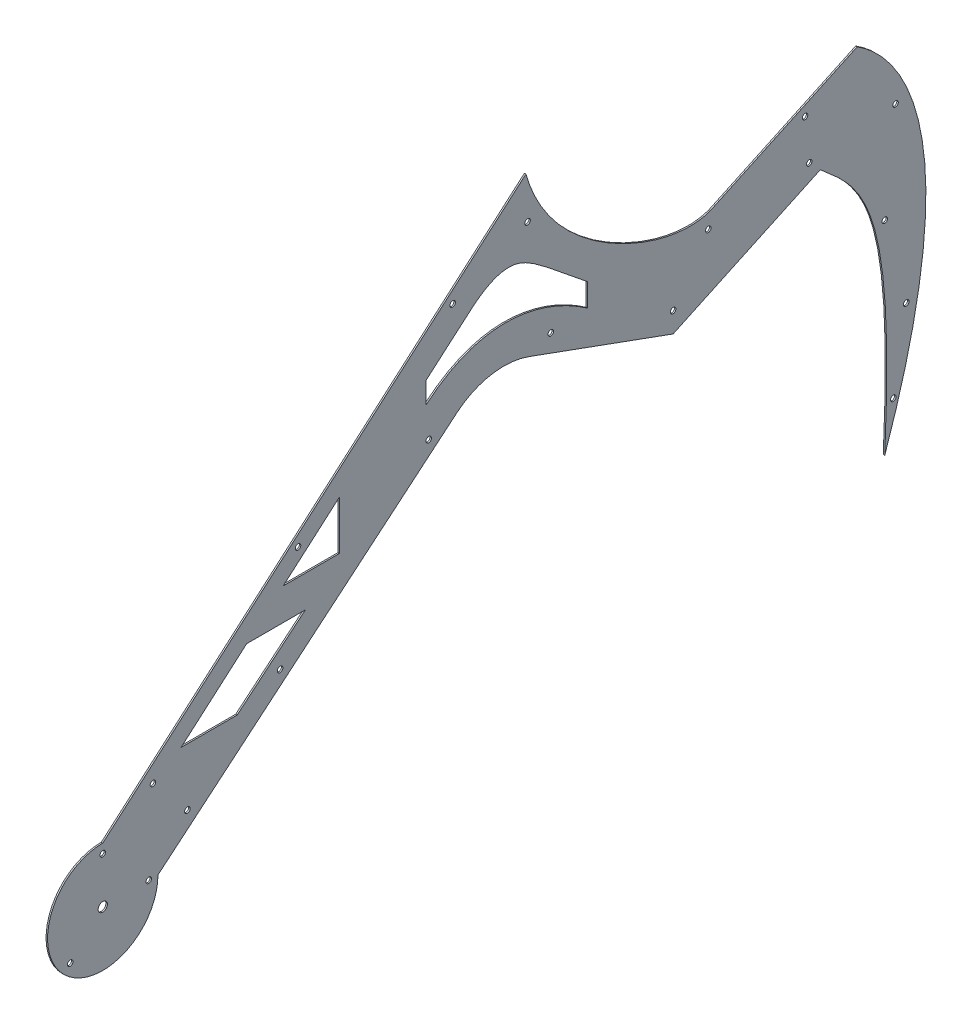
SolidWorks part; units mm, degrees
other "Markup1"
sketch "Sketch3" plane through (0, -30, -453.7149) normal (1, 0, 0) x (0, 0, -1)
ref_plane "Front Plane" through (0, 0, 0) normal (0, 0, 1) x (1, 0, 0)
ref_plane "Top Plane" through (0, 0, 0) normal (0, 1, 0) x (1, 0, 0)
ref_plane "Right Plane" through (0, 0, 0) normal (1, 0, 0) x (0, 0, -1)
sketch "Sketch2" plane through (0, 0, 0) normal (1, 0, 0) x (0, 0, -1)
  line L4 (-746.1189, 0) -> (2001.1162, 0) construction
  line L5 (0, 883.5315) -> (0, -632.2635) construction
  line L6 (0, 30) -> (230, 229.9359)
  line L7 (30, 0) -> (192.309, 136.1934)
  line L9 (231.7013, 143.1393) -> (310, 114.6409)
  line L10 (310, 114.6409) -> (390, 151.9455)
  line L11 (330, 162.4851) -> (410, 199.7897)
  line L12 (410, 199.7897) -> (437.0314, 182.9088) construction
  line L13 (437.0314, 182.9088) -> (470.3985, 130.1127) construction
  line L14 (390, 151.9455) -> (412.7624, 132.5357) construction
  line L15 (412.7624, 132.5357) -> (430.8798, 119.3594) construction
  line L16 (430.8798, 119.3594) -> (425.0344, 0) construction
  line L17 (470.3985, 130.1127) -> (425.0344, 0) construction
  line L18 (230, 229.9359) -> (239.3138, 197.0283) construction
  line L19 (239.3138, 197.0283) -> (264.964, 173.3238) construction
  line L20 (264.964, 173.3238) -> (307.757, 154.3394) construction
  line L21 (307.757, 154.3394) -> (330, 162.4851) construction
  line L22 (42.5631, 53.7494) -> (73.0482, 53.7494)
  line L24 (78.201, 84.729) -> (42.5631, 53.7494)
  line L25 (73.0482, 53.7494) -> (110.1371, 84.729)
  line L26 (110.1371, 84.729) -> (78.201, 84.729)
  line L27 (98.0934, 102.0212) -> (128.5785, 128.5214)
  line L28 (128.5785, 128.5214) -> (128.5785, 102.0212)
  line L29 (128.5785, 102.0212) -> (98.0934, 102.0212)
  line L30 (175.7455, 159.9984) -> (198.0041, 179.2063)
  line L31 (241.6174, 180.2232) -> (263.537, 162.4851)
  line L32 (198.0041, 179.2063) -> (218.9673, 198.4306) construction
  line L33 (218.9673, 198.4306) -> (227.9539, 188.9081) construction
  line L34 (227.9539, 188.9081) -> (231.4161, 188.3022) construction
  line L35 (231.4161, 188.3022) -> (241.6174, 180.2232) construction
  line L36 (175.7455, 148.428) -> (196.999, 166.4038) construction
  line L37 (196.999, 166.4038) -> (219.1847, 171.1458) construction
  line L38 (219.1847, 171.1458) -> (243.505, 164.1915) construction
  line L39 (243.505, 164.1915) -> (263.537, 150.0193) construction
  line L40 (175.7455, 159.9984) -> (175.7455, 148.428)
  line L41 (263.537, 162.4851) -> (263.537, 150.0193)
  line L42 (0, 25) -> (25, 0) construction
  line L43 (12.5, 12.5) -> (-27.6808, -27.6808) construction
  arc A0 (0, 30) -> (30, 0) centre (0, 0) ccw
  circle A1 centre (0, 0) radius 2.5
  arc A2 (192.309, 136.1934) -> (231.7013, 143.1393) centre (218.0205, 105.5516) cw
  circle A3 centre (96.409, 63.5562) radius 1.5
  circle A4 centre (25, 0) radius 1.5
  circle A5 centre (-17.6777, -17.6777) radius 1.5
  circle A6 centre (0, 25) radius 1.5
  circle A7 centre (27.2862, 44.4444) radius 1.5
  circle A8 centre (106.1435, 116.3066) radius 1.5
  circle A9 centre (177.163, 131.3169) radius 1.5
  circle A10 centre (190.1621, 188.6803) radius 1.5
  circle A11 centre (230.8867, 206.9706) radius 1.5
  circle A12 centre (243.505, 148.428) radius 1.5
  circle A13 centre (310, 125.634) radius 1.5
  circle A14 centre (329.1217, 154.3394) radius 1.5
  circle A15 centre (381.7045, 181.0784) radius 1.5
  circle A16 centre (383.9639, 158.1949) radius 1.5
  circle A17 centre (430.8798, 162.4851) radius 1.5
  circle A18 centre (425.0344, 110.6788) radius 1.5
  circle A19 centre (436.7166, 65.8476) radius 1.5
  circle A20 centre (429.6663, 24.5411) radius 1.5
  circle A21 centre (46, 22.5634) radius 1.5
  spline S0 degree 3 poles (410, 199.7897) (437.0314, 182.9088) (470.3985, 130.1127) (425.0344, 0) knots 0 0 0 0 1 1 1 1
  spline S1 degree 3 poles (390, 151.9455) (412.7624, 132.5357) (430.8798, 119.3594) (425.0344, 0) knots 0 0 0 0 1 1 1 1
  spline S2 degree 4 poles (230, 229.9359) (239.3138, 197.0283) (264.964, 173.3238) (307.757, 154.3394) (330, 162.4851) knots 0 0 0 0 0 1 1 1 1 1
  spline S3 degree 4 poles (198.0041, 179.2063) (218.9673, 198.4306) (227.9539, 188.9081) (231.4161, 188.3022) (241.6174, 180.2232) knots 0 0 0 0 0 1 1 1 1 1
  spline S4 degree 4 poles (175.7455, 148.428) (196.999, 166.4038) (219.1847, 171.1458) (243.505, 164.1915) (263.537, 150.0193) knots 0 0 0 0 0 1 1 1 1 1
  point P22 (210, 151.0379)
  dimension "D1" = 60
  dimension "D13" = 5
  dimension "D14" = 40
  dimension "D18" = 3
  dimension "D20" = 3
  dimension "D23" = 3
  dimension "D26" = 3
  dimension "D27" = 3
  dimension "D30" = 3
  dimension "D32" = 3
  dimension "D34" = 3
  dimension "D36" = 3
  dimension "D37" = 3
  dimension "D38" = 3
  dimension "D39" = 3
  dimension "D40" = 3
  dimension "D42" = 3
  dimension "D43" = 3
  dimension "D44" = 3
  dimension "D45" = 3
  dimension "D46" = 3
  dimension "D47" = 3
  dimension "D2" = 210
  dimension "D3" = 40
  dimension "D4" = 41
  dimension "D5" = 230
  dimension "D6" = 120
  dimension "D7" = 10
  dimension "D8" = 310
  dimension "D9" = 330
  dimension "D10" = 135
  dimension "D11" = 390
  dimension "D12" = 410
  dimension "D15" = 20
  dimension "D16" = 20
  dimension "D17" = 25
  dimension "D19" = 25
  dimension "D21" = 90
  dimension "D22" = 25
  dimension "D24" = 7
  dimension "D25" = 7
  dimension "D28" = 46
  dimension "D29" = 6
  dimension "D31" = 4.5
  dimension "D33" = 6
  dimension "D35" = 5
  dimension "D41" = 5
base flange "Base-Flange1" sketch "Sketch2" thickness 0.8 reverse thickness direction no parameters "D1"=0.7366
sketch "Bend-Lines1" plane through (0, 0, 0) normal (0, 1, 0) x (1, 0, 0)
sketch "Bounding-Box1" plane through (0, 0, 0) normal (0, 1, 0) x (1, 0, 0)
sheet metal parameters "Sheet-Metal1" thickness 0.8 parameters "D1"=0.7366
flat pattern "Flat-Pattern1"
sketch "Bend-Lines2" plane through (0, 0, 0) normal (0, 1, 0) x (1, 0, 0)
sketch3d "Bounding-Box2"
  line L0 (-27.8077, -32.0426, 0) -> (455.6066, 2.1633, 0) construction
  line L1 (-44.9683, 210.4795, 0) -> (438.446, 244.6854, 0) construction
  line L2 (-27.8077, -32.0426, 0) -> (-44.9683, 210.4795, 0) construction
  line L3 (455.6066, 2.1633, 0) -> (438.446, 244.6854, 0) construction
